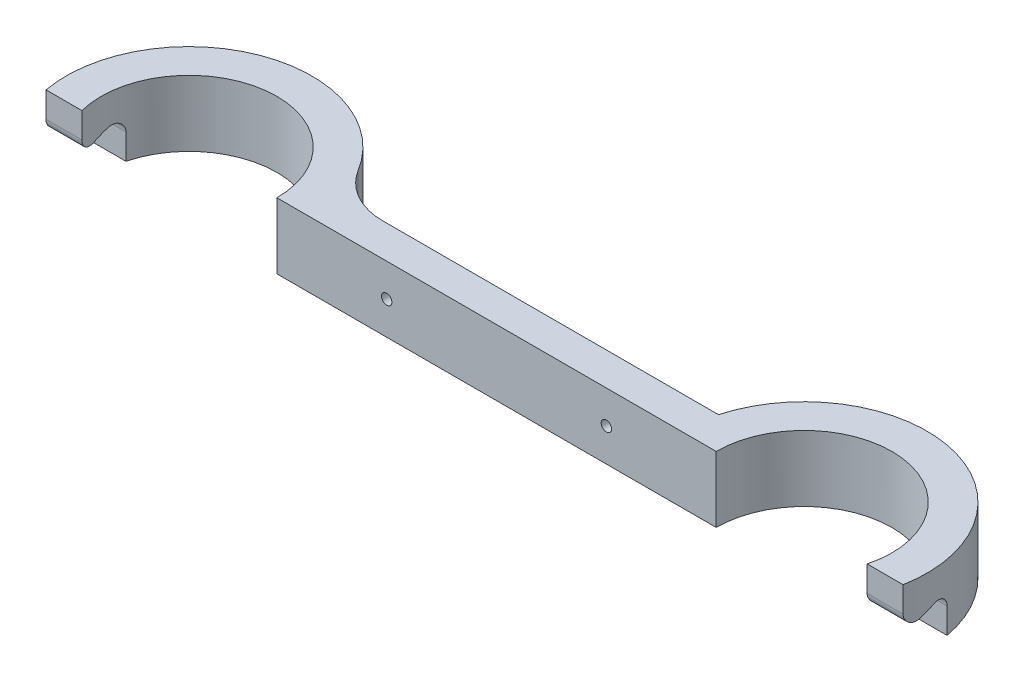
SolidWorks part; units mm, degrees
ref_plane "Front Plane" through (0, 0, 0) normal (0, 0, 1) x (1, 0, 0)
ref_plane "Top Plane" through (0, 0, 0) normal (0, 1, 0) x (1, 0, 0)
ref_plane "Right Plane" through (0, 0, 0) normal (1, 0, 0) x (0, 0, -1)
sketch "Sketch1" plane through (0, 0, 0) normal (0, 1, 0) x (1, 0, 0)
  line L0 (88.9, 0) -> (-88.9, 0) construction
  line L1 (54.6394, -9.525) -> (-54.6394, -9.525)
  line L2 (54.6394, -9.525) -> (54.6394, 9.525)
  line L3 (54.6394, 9.525) -> (-54.6394, 9.525)
  line L5 (54.6394, -9.525) -> (-54.6394, 9.525) construction
  line L6 (54.6394, 9.525) -> (-54.6394, -9.525) construction
  line L7 (-124.46, 0) -> (0, 0)
  line L8 (0, 9.525) -> (0, -9.525)
  circle A0 centre (-88.9, 0) radius 35.56
  circle A1 centre (-88.9, 0) radius 25.4
  point P0 (0, 0)
  point P11 (0, 0)
  dimension "D2" = 50.8
  dimension "D3" = 10.16
  dimension "D1" = 88.9
  dimension "D4" = 9.525
extrude "Boss-Extrude1" add sketch "Sketch1" along normal blind 19.05 contours A1 L7 A0 | A0 L7 L8 L3 region at (-26.8863, 0, -4.7816) region at (-93.5991, 0, -34.4458)
fillet "Fillet1" radius 19.05 1 edges at (-54.6394, 9.525, -9.525)
sketch "Sketch2" plane through (0, 0, -9.525) normal (0, 0, -1) x (-1, 0, 0)
  line L0 (0, 9.525) -> (31.75, 9.525) construction
  line L1 (0, 19.05) -> (0, 0) construction
  circle A0 centre (31.75, 9.525) radius 1.5
  dimension "D1" = 3
  dimension "D2" = 31.75
extrude "Cut-Extrude1" cut sketch "Sketch2" against normal through all both and the other way through all
ref_plane "Plane1" through (-124.46, 0, 0) normal (-1, 0, 0) x (0, 0, 1)
sketch "Sketch3" plane through (-124.46, 0, 0) normal (-1, 0, 0) x (0, 0, 1)
  line L0 (-6.35, 19.05) -> (6.35, 19.05)
  line L1 (6.35, 19.05) -> (6.35, 6.985)
  line L2 (6.35, 6.985) -> (-6.35, 12.065)
  line L3 (0, 19.05) -> (0, 0) construction
  line L4 (0, 9.525) -> (6.35, 9.525) construction
  line L5 (-6.35, 19.05) -> (-6.35, 12.065)
  line L6 (0, 19.05) -> (-35.56, 19.05) construction
  line L7 (-6.35, 12.065) -> (-6.35, 0)
  line L8 (-35.56, 0) -> (0, 0) construction
  line L9 (-6.35, 0) -> (6.35, 0)
  line L10 (6.35, 0) -> (6.35, 6.985)
  dimension "D1" = 2.54
  dimension "D2" = 2.54
  dimension "D3" = 12.7
  dimension "D4" = 6.35
extrude "Boss-Extrude2" add sketch "Sketch3" against normal up to surface (10.9666 mm away) contours L2 L4 L1 L0 L5 | L4 L2 L1 region at (-124.46, 14.5672, 0.3024) region at (-124.46, 8.6783, 4.2333) up to face at (-88.9, 9.525, -12.7)
extrude "Cut-Extrude3" cut sketch "Sketch3<3>" against normal up to surface and the other way through all contours L9 L10 L2 L7 region at (-124.46, 4.8754, -0.5644) up to face at (-97.7319, 9.1, -6.8412)
sketch "Sketch3<3>" plane through (-124.46, 0, 0) normal (-1, 0, 0) x (0, 0, 1) same geometry as "Sketch3"
sketch "Sketch4" plane through (0, 19.05, 0) normal (0, 1, 0) x (1, 0, 0)
  circle A0 centre (-88.9, 0) radius 35.56
  arc A1 (-58.5966, 18.607) -> (-123.8884, 6.35) centre (-88.9, 0) ccw construction
  line M9 (-124.46, -6.35) -> (-113.4934, -6.35)
  line M11 (-123.8884, 6.35) -> (-124.46, 6.35)
  line M12 (-124.46, 6.35) -> (-124.46, -6.35)
extrude "Cut-Extrude2" cut sketch "Sketch4" against normal through all both and the other way through all contours A0 M9 | A0 M11 M12 region at (-124.2888, 19.05, -4.7651) region at (-124.2888, 19.05, 4.7651)
fillet "Fillet2" radius 3.175 2 edges at (-118.6909, 6.985, 6.35) (-118.6909, 12.065, -6.35)
mirror "Mirror1" about plane through (0, 19.05, 0) normal (1, 0, 0) of "Cut-Extrude1", "Boss-Extrude2", "Boss-Extrude1", "Cut-Extrude3", "Fillet2"
sketch "Sketch5" plane through (0, 19.05, 0) normal (0, 1, 0) x (1, 0, 0)
  circle A0 centre (88.9, 0) radius 35.56
  arc A1 (123.8884, 6.35) -> (54.6394, 9.525) centre (88.9, 0) ccw construction
  line M2 (124.46, 6.35) -> (123.8884, 6.35)
  line M11 (113.4934, -6.35) -> (124.46, -6.35)
  line M12 (124.46, -6.35) -> (124.46, 6.35)
extrude "Cut-Extrude4" cut sketch "Sketch5" against normal through all both and the other way through all contours A0 M12 M2 | A0 M11 M12 region at (124.2888, 19.05, 4.7651) region at (124.2888, 19.05, -4.7651)
